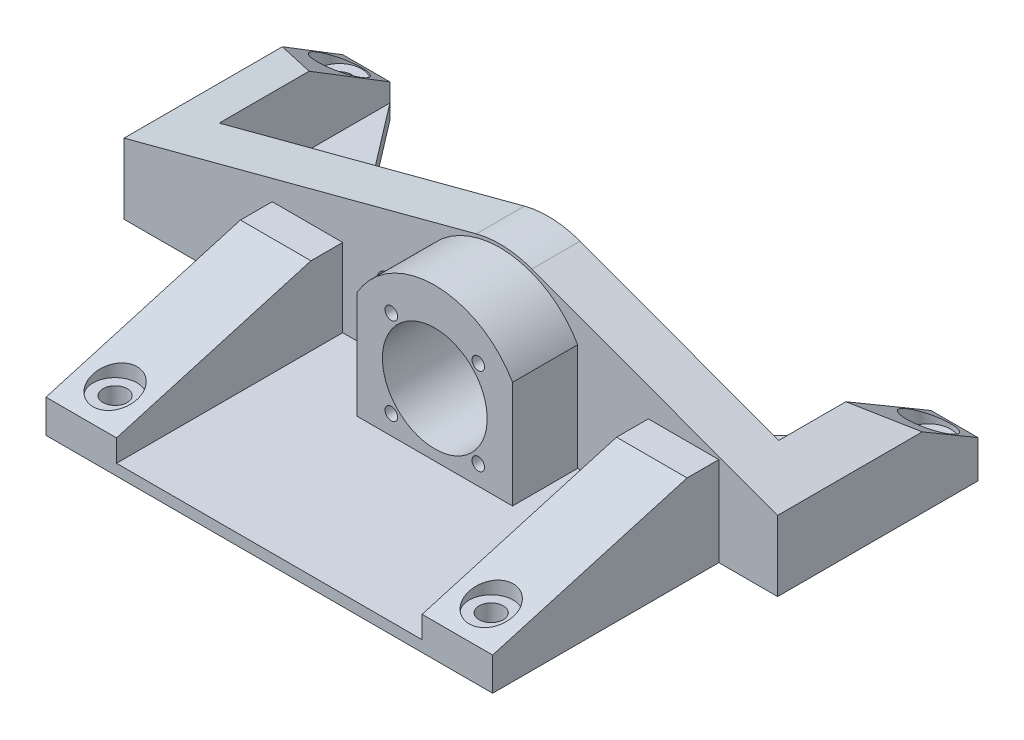
SolidWorks part; units mm, degrees
material "SuperPLA"
ref_plane "Front Plane" through (0, 0, 0) normal (0, 0, 1) x (1, 0, 0)
ref_plane "Top Plane" through (0, 0, 0) normal (0, 1, 0) x (1, 0, 0)
ref_plane "Right Plane" through (0, 0, 0) normal (1, 0, 0) x (0, 0, -1)
sketch "Sketch2" plane through (0, 0, 0) normal (0, 1, 0) x (1, 0, 0)
  line L1 (-176.53, 0) -> (0, 0)
  line L2 (-176.53, 0) -> (-176.53, 28.1)
  line L3 (-176.53, 28.1) -> (0, 28.1)
  line L4 (0, 0) -> (0, 28.1)
  dimension "D1" = 176.53
  dimension "D2" = 28.1
extrude "Boss-Extrude1" add sketch "Sketch2" along normal blind 5
sketch "Sketch3" plane through (0, 0, 0) normal (0, 0, -1) x (-1, 0, 0)
  line L0 (0, 5) -> (176.53, 5) construction
  line L2 (0, 0) -> (176.53, 0) construction
  line L3 (0, 0) -> (176.53, 0)
  line L6 (0, 0) -> (0, 19)
  line L7 (0, 19) -> (66.3539, 43.4573)
  line L9 (176.53, 19) -> (176.53, 0)
  line L11 (60, 5) -> (90, 5) construction
  line L12 (60, 5) -> (60, 35) construction
  line L13 (60, 35) -> (90, 35) construction
  line L14 (90, 5) -> (90, 35) construction
  line L15 (60, 5) -> (90, 35) construction
  line L16 (60, 35) -> (90, 5) construction
  line L17 (81.3939, 44.1685) -> (176.53, 19)
  circle A0 centre (75, 20) radius 6.6359
  circle A2 centre (105, 20) radius 7 construction
  circle A3 centre (105, 20) radius 3.325
  arc A5 (66.3539, 43.4573) -> (81.3939, 44.1685) centre (75, 20) cw
  point P11 (0, 17.3262)
  point P13 (0, 0)
  point P15 (46.5433, 30.7827)
  point P19 (75.9816, 20)
  point P24 (154.0382, 21.1503)
  point P25 (160.7866, 0)
  point P26 (0, 0)
  point P27 (51.6855, 29.024)
  point P28 (0, 0)
  dimension "D1" = 15
  dimension "D3" = 14
  dimension "D5" = 6.65
  dimension "D6" = 25
  dimension "D2" = 75
  dimension "D4" = 30
  dimension "D7" = 176.53
  dimension "D8" = 19
extrude "Boss-Extrude2" add sketch "Sketch3" against normal blind 5 separate body
ref_plane "Plane1" through (0, 0, -33.1) normal (0, 0, 1) x (1, 0, 0)
sketch "Sketch4" plane through (0, 0, -33.1) normal (0, 0, 1) x (1, 0, 0)
  line L4 (-176.53, 19) -> (-176.53, 0)
  line L5 (-176.53, 0) -> (0, 0)
  line L6 (-176.53, 19) -> (-176.53, 0)
  line L9 (-176.53, 0) -> (0, 0)
  line L14 (0, 0) -> (0, 19)
  line L15 (0, 0) -> (0, 19)
  line L16 (0, 19) -> (-66.3539, 43.4573)
  line L17 (0, 19) -> (-66.3539, 43.4573)
  line L20 (-81.3939, 44.1685) -> (-176.53, 19)
  line L21 (-81.3939, 44.1685) -> (-176.53, 19)
  circle A1 centre (-75, 20) radius 6.6359
  circle A2 centre (-75, 20) radius 6.6359
  circle A3 centre (-105, 20) radius 3.325
  circle A4 centre (-105, 20) radius 3.325
  arc A5 (-66.3539, 43.4573) -> (-81.3939, 44.1685) centre (-75, 20) ccw
  arc A6 (-66.3539, 43.4573) -> (-81.3939, 44.1685) centre (-75, 20) ccw
  dimension "D1" = 0
  dimension "D2" = 0
  dimension "D3" = 0
extrude "Boss-Extrude3" add sketch "Sketch4" along normal blind 5 separate body
sketch "Sketch5" plane through (0, 5, 0) normal (0, 1, 0) x (1, 0, 0)
  line L0 (0, 28.1) -> (0, 34.1)
  line L1 (-8.2318, 40.1647) -> (-47.1136, 28.1)
  line L2 (0, 28.1) -> (-176.53, 28.1) construction
  line L3 (-47.1136, 28.1) -> (0, 28.1)
  line L4 (0, 0) -> (0, -42.25)
  line L5 (-45.0251, 0) -> (-11.4804, -45.9919)
  line L6 (-176.53, 0) -> (0, 0) construction
  line L7 (0, 0) -> (-45.0251, 0)
  circle A0 centre (-6.35, 34.1) radius 3.175
  arc A1 (0, 34.1) -> (-8.2318, 40.1647) centre (-6.35, 34.1) ccw
  circle A2 centre (-6.35, -42.25) radius 3.8905
  arc A3 (-11.4804, -45.9919) -> (0, -42.25) centre (-6.35, -42.25) ccw
  dimension "D1" = 6.35
  dimension "D2" = 12.7
  dimension "D4" = 76.35
  dimension "D3" = 6
extrude "Boss-Extrude4" add sketch "Sketch5" against normal up to surface (5 mm away) up to face at (-88.265, 0, -14.05)
sketch "Sketch7" plane through (0, 0, 5) normal (0, 0, 1) x (1, 0, 0)
  line L1 (-90.25, 4.75) -> (-59.75, 4.75)
  line L2 (-90.25, 4.75) -> (-90.25, 35.25)
  line L3 (-90.25, 35.25) -> (-59.75, 35.25)
  line L4 (-59.75, 4.75) -> (-59.75, 35.25)
  line L5 (-90.25, 4.75) -> (-59.75, 35.25) construction
  line L6 (-90.25, 35.25) -> (-59.75, 4.75) construction
  point P0 (-75, 20)
  dimension "D1" = 30.5
sketch "Sketch9" plane through (0, 0, 5) normal (0, 0, 1) x (1, 0, 0)
  line L1 (-63.25, 8.25) -> (-86.75, 8.25) construction
  line L2 (-63.25, 8.25) -> (-63.25, 31.75) construction
  line L3 (-63.25, 31.75) -> (-86.75, 31.75) construction
  line L4 (-86.75, 8.25) -> (-86.75, 31.75) construction
  line L5 (-63.25, 8.25) -> (-86.75, 31.75) construction
  line L6 (-63.25, 31.75) -> (-86.75, 8.25) construction
  circle A0 centre (-75, 20) radius 14.15
  circle A1 centre (-75, 20) radius 24.15
  circle A2 centre (-86.75, 31.75) radius 1.7
  circle A4 centre (-63.25, 31.75) radius 1.7
  circle A5 centre (-63.25, 8.25) radius 1.7
  circle A6 centre (-86.75, 8.25) radius 1.7
  point P18 (-75, 20)
  dimension "D1" = 28.3
  dimension "D2" = 3.4
  dimension "D3" = 23.5
  dimension "D5" = 10
  dimension "D4" = 4
extrude "Boss-Extrude5" add sketch "Sketch9" along normal blind 20.6
extrude "Cut-Extrude2" cut sketch "Sketch7" against normal blind 26.6
sketch "Sketch11" plane through (0, 0, 0) normal (1, 0, 0) x (0, 0, -1)
  line L1 (28.1, 0) -> (42.275, 0)
  line L2 (42.275, 0) -> (42.275, 8)
  line L3 (42.275, 8) -> (37.1, 18)
  line L4 (37.1, 18) -> (28.1, 18)
  line L6 (37.275, 5) -> (30.925, 5) construction
  line L8 (37.275, 5) -> (30.925, 5) construction
  line L10 (28.1, 19) -> (28.1, 43.4573) construction
  line L13 (28.1, 0) -> (28.1, 19) construction
  line L14 (28.1, 0) -> (28.1, 18)
  dimension "D3" = 5
  dimension "D4" = 9
  dimension "D6" = 18
extrude "Boss-Extrude6" add sketch "Sketch11" against normal blind 12.7 separate body
sketch "Sketch13" plane through (0, 0, 0) normal (0, -1, 0) x (1, 0, 0)
  circle A0 centre (-6.35, -34.1) radius 3.175 construction
  point P0 (-25.4, 64.96)
  point P1 (-127, 64.96)
  point P4 (-171.7518, -42.3427)
  point P5 (-6.35, -34.1)
  point P6 (-170.18, -38.81)
  dimension "D1" = 99.06
  dimension "D2" = 101.6
  dimension "D3" = 19.05
  dimension "D4" = 4.71
  dimension "D5" = 163.83
ref_plane "Plane2" through (-25.4, 0, 0) normal (1, 0, 0) x (0, 0, -1)
ref_plane "Plane3" through (-127, 0, 0) normal (1, 0, 0) x (0, 0, -1)
sketch "Sketch14" plane through (-25.4, 0, 0) normal (1, 0, 0) x (0, 0, -1)
  line L0 (-74.0991, 0) -> (-5, 0)
  line L1 (-5, 0) -> (-5, 24.1178)
  line L2 (-5, 43.4573) -> (-5, 19) construction
  line L3 (-5, 24.1178) -> (-21.575, 24.1178)
  line L4 (-21.575, 24.1178) -> (-74.0991, 8.9442)
  line L5 (-74.0991, 8.9442) -> (-74.0991, 0)
extrude "Boss-Extrude7" add sketch "Sketch14" along normal mid plane 19.05
sketch "Sketch15" plane through (-127, 0, 0) normal (1, 0, 0) x (0, 0, -1)
  line L0 (-74.0991, 8.9442) -> (-74.0991, 0) construction
  line L1 (-74.0991, 8.9442) -> (-74.0991, 0)
  line L2 (-74.0991, 0) -> (-5, 0)
  line L3 (-5, 0) -> (-5, 24.1178)
  line L6 (-21.575, 24.1178) -> (-74.0991, 8.9442) construction
  line L7 (-5, 24.1178) -> (-21.575, 24.1178) construction
  line L8 (-21.575, 24.1178) -> (-74.0991, 8.9442)
  line L9 (-5, 24.1178) -> (-21.575, 24.1178)
  point P9 (-5, 23.4303)
extrude "Boss-Extrude8" add sketch "Sketch15" along normal mid plane 19.05
delete or keep bodies "Body-Delete/Keep 2" type delete bodies bodies 104
sketch "Sketch16" plane through (0, 0, 0) normal (0, -1, 0) x (1, 0, 0)
  line L1 (-117.475, 74.0991) -> (-34.925, 74.0991)
  line L2 (-117.475, 74.0991) -> (-117.475, 5)
  line L3 (-117.475, 5) -> (-34.925, 5)
  line L4 (-34.925, 74.0991) -> (-34.925, 5)
extrude "Boss-Extrude9" add sketch "Sketch16" against normal blind 3
other "DeleteFace1" face at (-61.55, 8.25, 25.6) face at (-75, -2.075, 15.3) face at (-75, -2.075, 5) and patch yes
delete or keep bodies "Body-Delete/Keep 3" type delete bodies bodies 109 103
ref_plane "Plane4" through (-170.18, 0, 0) normal (-1, 0, 0) x (0, 0, 1)
ref_plane "Plane5" through (-6.35, 0, 0) normal (1, 0, 0) x (0, 0, -1)
sketch "Sketch17" plane through (-6.35, 0, 0) normal (1, 0, 0) x (0, 0, -1)
  line L0 (0, 0) -> (41.1354, 0)
  line L1 (41.1354, 0) -> (41.1354, 10.1341)
  line L2 (41.1354, 10.1341) -> (10.3486, 28.2655)
  line L3 (10.3486, 28.2655) -> (0, 28.2655)
  line L4 (0, 28.2655) -> (0, 0)
  point P6 (0, 28.2655)
extrude "Boss-Extrude10" add sketch "Sketch17" along normal mid plane 12.7 separate body
sketch "Sketch18" plane through (-170.18, 0, 0) normal (-1, 0, 0) x (0, 0, 1)
  line L0 (-46.1063, 0) -> (0, 0)
  line L1 (-46.1063, 0) -> (-46.1063, 8.9497)
  line L2 (-46.1063, 8.9497) -> (-15.6624, 27.651)
  line L3 (-15.6624, 27.651) -> (0, 27.651)
  line L4 (0, 27.651) -> (0, 0)
  line L5 (-41.1354, 10.1341) -> (-10.3486, 28.2655) construction
extrude "Boss-Extrude11" add sketch "Sketch18" along normal mid plane 12.7 separate body
ref_plane "Plane6" through (0, 9.525, 0) normal (0, -1, 0) x (-1, 0, 0)
sketch "Sketch19" plane through (0, 9.525, 0) normal (0, -1, 0) x (-1, 0, 0)
  point P0 (6.35, 34.1)
  point P3 (25.4, -64.96)
  point P6 (127, -64.96)
  point P9 (170.18, 38.81)
hole_wizard "CBORE for 1/4 Button Head Cap Screw1" positions "Sketch19" profile "Sketch20" counterbore size "1/4" standard "ANSI Inch" end condition through all
sketch "Sketch20" plane through (-6.35, 9.525, -34.1) normal (1, 0, 0) x (0, 0, 1)
  line L0 (0, 0) -> (0, 9.525)
  line L1 (0, 9.525) -> (3.2639, 9.525)
  line L3 (3.2639, 9.525) -> (3.2639, 0.0254)
  line L4 (3.2639, 0.0254) -> (5.9538, 0.0254)
  line L5 (5.9538, 0.0254) -> (5.9538, 0)
  line L7 (5.9538, 0) -> (0, 0)
  line L11 (0, -6.35) -> (0, 107.95) construction
  dimension "Thru Hole Dia." = 6.5278
  dimension "Thru Hole Depth" = 9.525
  dimension "C'Bore Dia." = 11.9075
  dimension "C'Bore Depth" = 0.0254
sketch "Sketch21" plane through (0, 9.525, 0) normal (0, -1, 0) x (1, 0, 0)
  circle A0 centre (-6.35, -34.1) radius 5.9538 construction
  circle A1 centre (-25.4, 64.96) radius 5.9538 construction
  circle A2 centre (-127, 64.96) radius 5.9538 construction
  circle A3 centre (-170.18, -38.81) radius 5.9538 construction
  circle A4 centre (-6.35, -34.1) radius 5.9538
  circle A5 centre (-25.4, 64.96) radius 5.9538
  circle A6 centre (-127, 64.96) radius 5.9538
  circle A7 centre (-170.18, -38.81) radius 5.9538
extrude "Cut-Extrude3" cut sketch "Sketch21" against normal through all
sketch "Sketch23" plane through (0, 0, 25.6) normal (0, 0, 1) x (1, 0, 0)
  line L0 (-96, 31.9257) -> (-96, 3) construction
  line L1 (-117.475, 3) -> (-92.1529, 3) construction
  line L2 (-96, 3) -> (-54, 3) construction
  line L3 (-34.925, 3) -> (-117.475, 3) construction
  line L4 (-75, 20) -> (-75, 3) construction
  line L5 (-54, 3) -> (-54, 31.9257) construction
  line L7 (-96, 31.9257) -> (-104, 31.9257)
  line L8 (-96, 31.9257) -> (-96, 3)
  line L9 (-96, 3) -> (-104, 3)
  line L10 (-104, 31.9257) -> (-104, 3)
  line L11 (-54, 31.9257) -> (-46, 31.9257)
  line L12 (-54, 31.9257) -> (-54, 3)
  line L13 (-54, 3) -> (-46, 3)
  line L14 (-46, 31.9257) -> (-46, 3)
  arc A0 (-57.8471, 3) -> (-92.1529, 3) centre (-75, 20) ccw construction
  point P1 (-96, 35.177)
  point P15 (0, 0)
  point P17 (-54, 3.3962)
  point P21 (0, 0)
  dimension "D1" = 42
  dimension "D2" = 8
extrude "Cut-Extrude4" cut sketch "Sketch23" against normal up to surface (20.6 mm away) up to face at (-108.325, 20, 5)
other "DeleteFace5" face at (-94.1604, 5.4735, 15.3) face at (-55.8396, 5.4735, 15.3) and patch yes
split "Split1" bodies to split 121 resulting bodies 125 126 split by face at (-33.177, 31.2287, 2.5)
delete or keep bodies "Body-Delete/Keep 4" type delete bodies bodies 126
split "Split2" bodies to split 122 resulting bodies 127 128 split by face at (-128.9619, 31.5843, 2.5)
delete or keep bodies "Body-Delete/Keep 5" type delete bodies bodies 127
sketch "Sketch24" plane through (0, 0, 0) normal (0, -1, 0) x (1, 0, 0)
  line L0 (-163.83, -46.1063) -> (-139.0837, -13.7381)
  line L1 (-139.0837, -13.7381) -> (-40.8001, -13.7381)
  line L2 (-40.8001, -13.7381) -> (-12.7, -41.1354)
  line L3 (-12.7, 0) -> (-12.7, -41.1354) construction
  line L4 (0, 0) -> (-176.53, 0) construction
  line L5 (-163.83, -46.1063) -> (-163.83, 0) construction
  line L6 (-12.7, 0) -> (-12.7, -41.1354)
  line L7 (-12.7, 0) -> (-163.83, 0)
  line L8 (-163.83, -46.1063) -> (-163.83, 0)
  point P6 (-37.8911, -19.8004)
  point P10 (-137.7006, -11.9289)
  point P12 (-40.8001, -13.7381)
extrude "Boss-Extrude12" add sketch "Sketch24" against normal blind 4
other "Move Face3" face at (-75, 20.5189, 25.6) offset 5 parameters "D1"=5
other "Move Face4" flip direction yes face at (-89.15, 20, 5) offset 5 parameters "D1"=5
fillet "Fillet1" radius 2 4 edges at (-90.25, 4.75, 5) (-90.25, 35.25, 5) (-59.75, 35.25, 5) (-59.75, 4.75, 5)
other "Move Face5" face at (-108.325, 20, 5) offset 8 parameters "D1"=8
